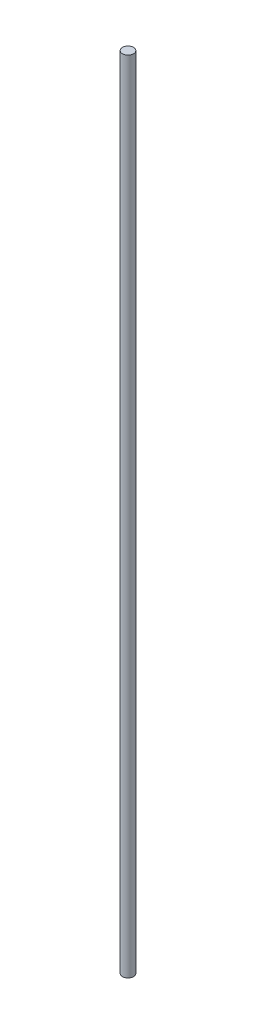
SolidWorks part; units mm, degrees
material "AISI 1020"
ref_plane "Front Plane" through (0, 0, 0) normal (0, 0, 1) x (1, 0, 0)
ref_plane "Top Plane" through (0, 0, 0) normal (0, 1, 0) x (1, 0, 0)
ref_plane "Right Plane" through (0, 0, 0) normal (1, 0, 0) x (0, 0, -1)
sketch "Sketch1" plane through (0, 0, 0) normal (0, 1, 0) x (1, 0, 0)
  circle A0 centre (0, 0) radius 2.5
  dimension "D1" = 5
extrude "Boss-Extrude1" add sketch "Sketch1" along normal blind 180 and the other way blind 180
cosmetic thread "Cosmetic Thread1" parameters "D2"=4.11
